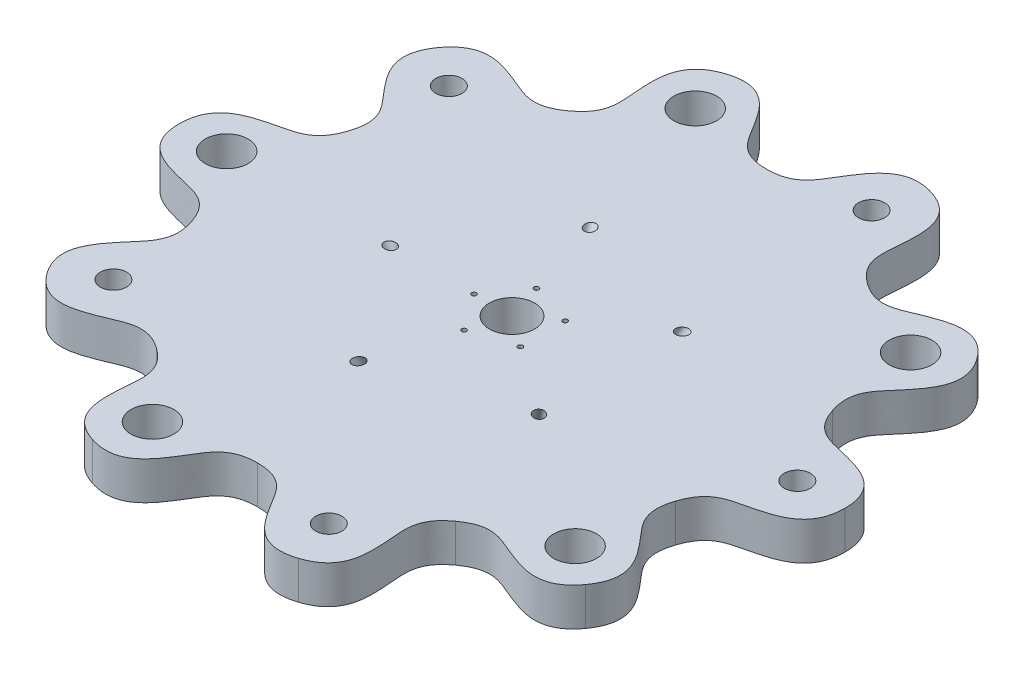
SolidWorks part; units mm, degrees
other "Markup1"
sketch "Sketch22" plane through (67.4, 16.5, 67.4) normal (0.6133, 0.6241, 0.4841) x (0.6587, -0.0661, -0.7495)
sketch "Sketch37" plane through (67.4, 28, 67.4) normal (0.6133, 0.6241, 0.4841) x (0.6587, -0.0661, -0.7495)
other "Markup2"
sketch "Sketch23" plane through (67.4, 26.5, 67.4) normal (0.1362, 0.0894, 0.9866) x (0.9893, -0.0646, -0.1307)
sketch "Sketch38" plane through (67.4, 28, 67.4) normal (0.1362, 0.0894, 0.9866) x (0.9893, -0.0646, -0.1307)
other "Markup5"
sketch "Sketch28" plane through (-67.4, 30.5, 67.4) normal (-0.0176, 0.5562, 0.8308) x (0.9998, 0.0146, 0.0115)
sketch "Sketch39" plane through (-67.4, 28, 67.4) normal (-0.0176, 0.5562, 0.8308) x (0.9998, 0.0146, 0.0115)
material "1023 Carbon Steel Sheet (SS)"
ref_plane "Front Plane" through (0, 0, 0) normal (0, 0, 1) x (1, 0, 0)
ref_plane "Top Plane" through (0, 0, 0) normal (0, 1, 0) x (1, 0, 0)
ref_plane "Right Plane" through (0, 0, 0) normal (1, 0, 0) x (0, 0, -1)
sketch "Sketch1" plane through (0, 0, 0) normal (0, 0, 1) x (1, 0, 0)
  line L5 (-47.4, 0) -> (-47.4, -8)
  line L9 (-7, -8) -> (0, -8)
  line L10 (0, -8) -> (0, 0)
  line L12 (-7, -8) -> (-17.4, -8)
  line L24 (-17.4, -8) -> (-47.4, -8)
  line L25 (-47.4, 0) -> (0, 0)
  dimension "D2" = 8
  dimension "D3" = 47.4
  dimension "D8" = 0
  dimension "D10" = 7
revolve "Revolve1" add sketch "Sketch1" angle 360 about L10
sketch "Sketch4" plane through (0, 0, 0) normal (0, 0, 1) x (1, 0, 0)
  line L0 (0, 0) -> (0, 13.3666) construction
sketch "Sketch2" plane through (0, 0, 0) normal (0, 1, 0) x (1, 0, 0)
  circle A0 centre (-8, 0) radius 0.5
  dimension "D2" = 1
  dimension "D1" = 8
extrude "Fuel holes" cut sketch "Sketch2" against normal up to next from offset 5
pattern_circular "CirPattern1" count 5 over 360 about axis through (0, 0, 0) along (0, 1, 0) of "Fuel holes" reverse direction yes
sketch "Sketch5" plane through (0, 0, 0) normal (1, 0, 0) x (0, 0, -1)
sketch "Sketch19" plane through (0, -8, 0) normal (0, -1, 0) x (1, 0, 0)
  line L0 (-47.4, 0) -> (-70, 0) construction
  line L1 (-56.6312, -41.145) -> (0, 0) construction
  line L4 (0, 0) -> (-66.574, -21.6312) construction
  line L5 (-51.8483, -13.5569) -> (-50.8815, -16.5324) construction
  line L9 (-69, 0) -> (-70, 0)
  line L11 (-53.7996, 39.0877) -> (-54.2257, 38.5013)
  circle A1 centre (0, 0) radius 47.4
  circle A2 centre (0, 0) radius 70 construction
  circle A3 centre (-60, 0) radius 4.5
  circle A4 centre (0, 0) radius 47.4 construction
  circle A5 centre (-48.541, -35.2671) radius 2.75
  circle A6 centre (0, 0) radius 53.5
  circle A8 centre (0, 0) radius 70
  spline S0 degree 3 poles (-50.8815, -16.5324) (-52.4491, -11.7078) (-59.9998, -9.5551) (-70, -7.7496) (-70, 0) knots 0 0 0 0 0.376166 1 1 1 1
  spline S1 degree 3 poles (-50.8815, -16.5324) (-49.3139, -21.357) (-54.1572, -27.5367) (-61.1863, -34.8754) (-56.6312, -41.145) knots 0 0 0 0 0.376166 1 1 1 1
  circle M22 centre (0, 0) radius 47.4
  dimension "D2" = 9
  dimension "D5" = 5.5
  dimension "D7" = 107
  dimension "D3" = 60
  dimension "D4" = 36
  dimension "D6" = 60
  dimension "D8" = 18
  dimension "D1" = 22.6
extrude "Boss-Extrude2" add sketch "Sketch19" against normal blind 8 contours A6 S1 A8 S0 A3 A5 | S1 S0 A8 | A3 | A5 | A6 M22 region at (-60, -8, 0) region at (-48.541, -8, -35.2671) region at (8.1325, -8, -51.3467) region at (-61.1052, -8, -7.4539) region at (-60.0877, -8, -19.5238)
extrude "Bolt holes" cut sketch "Sketch19<3>" against normal up to surface (8 mm away) contours A3 | A5 up to face at (-1.9721, 0, -7.6085)
sketch "Sketch19<3>" plane through (0, -8, 0) normal (0, -1, 0) x (1, 0, 0) same geometry as "Sketch19"
extrude "Grooves" cut sketch "Sketch19<8>" against normal through all contours S1 S0 A8 region at (-60.0877, -8, -19.5238)
sketch "Sketch19<8>" plane through (0, -8, 0) normal (0, -1, 0) x (1, 0, 0) same geometry as "Sketch19"
sketch "Sketch21" plane through (0, 0, 0) normal (0, 0, 1) x (1, 0, 0)
  line L0 (0, 0) -> (51.8972, 0) construction
  line L1 (0, 0) -> (0, -5.4672) construction
sketch "Sketch8" plane through (-29.8564, -8, 0) normal (0, -1, 0) x (-1, 0, 0)
  line L0 (-29.8564, 0) -> (-8.8564, 0) construction
  line L1 (-8.8564, 0) -> (-8.8564, 32.0516) construction
  circle A2 centre (-8.8564, 0) radius 1.75
  dimension "D1" = 3.5
  dimension "D2" = 21
ref_plane "Plane1" through (-21, 0, 0) normal (1, 0, 0) x (0, 0, -1)
ref_plane "Plane2" through (-1.7859, 3.0933, 0) normal (0.5, -0.866, 0) x (0, 0, -1)
sketch "Sketch41" plane through (-1.7859, 3.0933, 0) normal (0.5, -0.866, 0) x (0, 0, -1)
  circle A0 centre (0, -22.1865) radius 1.15
  dimension "D1" = 2.3
extrude "Cut-Extrude7" cut sketch "Sketch41" against normal blind 10 and the other way through all
sketch "Sketch31" plane through (0, -8, 0) normal (0, -1, 0) x (1, 0, 0)
  circle A0 centre (0, 0) radius 27.4
  dimension "D1" = 54.8
sketch "Sketch32" plane through (0, 0, 0) normal (0, 1, 0) x (1, 0, 0)
  circle A0 centre (0, 0) radius 5.5 construction
  circle A1 centre (0, 0) radius 4.75
  dimension "M11_threads" = 11
  dimension "M11Tap" = 9.5
sketch "Sketch35" plane through (0, 0, 0) normal (0, 0, 1) x (1, 0, 0)
  line L0 (0, 0) -> (0, 22.3821) construction
pattern_circular "CirPattern9" count 5 over 360 about axis through (0, 0, 0) along (0, 1, 0) of "Cut-Extrude7"
pattern_circular "CirPattern10" count 5 over 360 about axis through (0, 0, 0) along (0, 1, 0) of "Bolt holes"
pattern_circular "CirPattern11" count 10 over 360 about axis through (0, 0, 0) along (0, 1, 0) of "Grooves"
extrude "M11Tap" cut sketch "Sketch32" against normal through all contours A1
equation "\"Bolts\"= 10"
equation "\"D4@Sketch19\"=360/\"Bolts\""
equation "\"D7@Sketch19\"=102+2.5*2"
equation "\"D8@Sketch19\"=\"D4@Sketch19\"/2"
